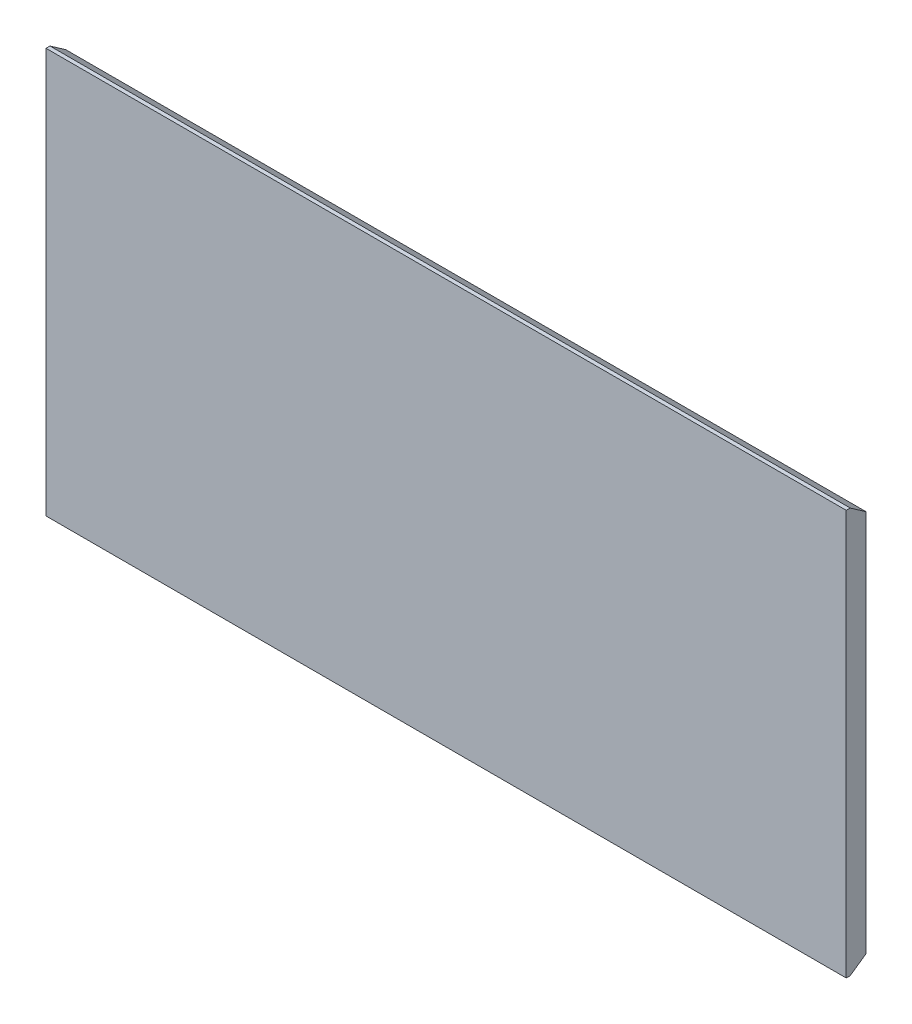
SolidWorks part; units mm, degrees
ref_plane "前视基准面" through (0, 0, 0) normal (0, 0, 1) x (1, 0, 0)
ref_plane "上视基准面" through (0, 0, 0) normal (0, 1, 0) x (1, 0, 0)
ref_plane "右视基准面" through (0, 0, 0) normal (1, 0, 0) x (0, 0, -1)
sketch "草图1" plane through (0, 0, 0) normal (0, 0, 1) x (1, 0, 0)
  line L1 (-202.5, 102.5) -> (202.5, 102.5)
  line L2 (-202.5, 102.5) -> (-202.5, -102.5)
  line L3 (-202.5, -102.5) -> (202.5, -102.5)
  line L4 (202.5, 102.5) -> (202.5, -102.5)
  line L5 (-202.5, 102.5) -> (202.5, -102.5) construction
  line L6 (-202.5, -102.5) -> (202.5, 102.5) construction
  point P0 (0, 0)
  dimension "D1" = 405
  dimension "D2" = 205
base flange "基体-法兰1" sketch "草图1" thickness 10 reverse thickness direction no parameters "D1"=1
chamfer "倒角1" distance 8 angle 35 1 edges at (0, 102.5, -10) first distance on face at (0, 102.5, -5)
chamfer "倒角2" distance 8 angle 35 1 edges at (0, -102.5, -10) first distance on face at (0, -102.5, -5)
sketch "折弯-线1" plane through (0, 0, 0) normal (0, 1, 0) x (1, 0, 0)
sketch "边界框1" plane through (0, 0, 0) normal (0, 1, 0) x (1, 0, 0)
sheet metal parameters "钣金6" thickness 10 parameters "D1"=1
flat pattern "平板型式6" [suppressed]
sketch "折弯-线2" plane through (0, 0, 0) normal (0, 1, 0) x (1, 0, 0)
sketch "边界框2" [suppressed] plane through (0, 0, 0) normal (0, 1, 0) x (1, 0, 0)
